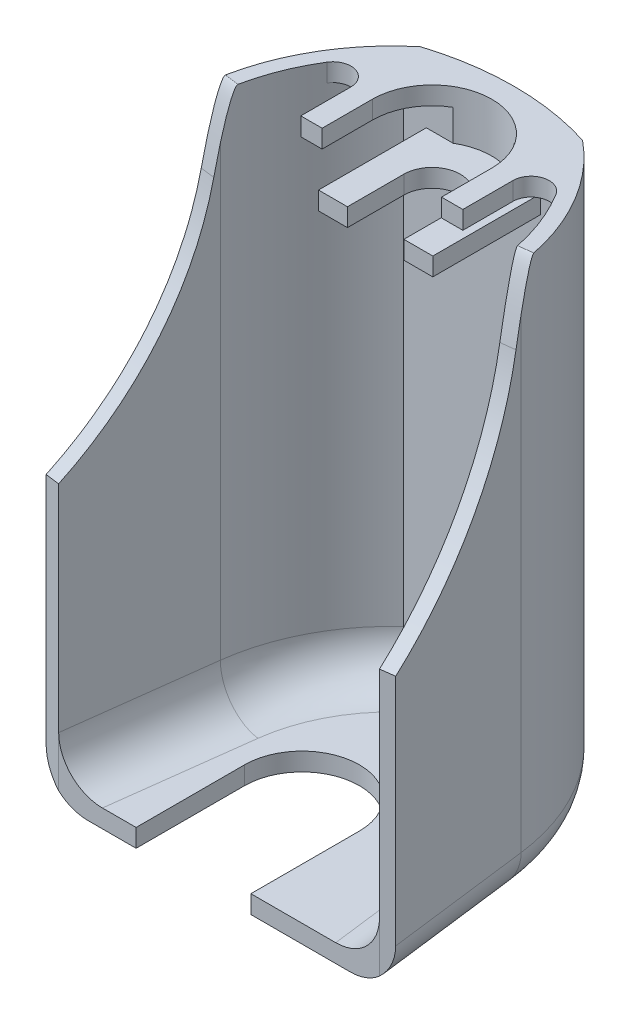
SolidWorks part; units mm, degrees
material "ABS"
ref_plane "Front Plane" through (0, 0, 0) normal (0, 0, 1) x (1, 0, 0)
ref_plane "Top Plane" through (0, 0, 0) normal (0, 1, 0) x (1, 0, 0)
ref_plane "Right Plane" through (0, 0, 0) normal (1, 0, 0) x (0, 0, -1)
sketch "Sketch1" plane through (0, 0, 0) normal (0, 1, 0) x (1, 0, 0)
  line L6 (-7.493, 9.017) -> (7.493, 9.017)
  line L10 (-4.953, 0) -> (-4.953, -7.493)
  line L11 (4.953, 0) -> (4.953, -7.493)
  line L14 (-7.493, -9.9072) -> (-4.953, -9.9072)
  line L15 (-4.953, -9.9072) -> (-4.953, -7.493)
  line L16 (4.953, -7.493) -> (4.953, -9.9072)
  line L17 (4.953, -9.9072) -> (7.493, -9.9072)
  line L19 (-7.493, 9.017) -> (-10.033, 9.017)
  line L20 (-10.033, 9.017) -> (-10.033, -9.9072)
  line L21 (-10.033, -9.9072) -> (-7.493, -9.9072)
  line L22 (7.493, 9.017) -> (10.033, 9.017)
  line L23 (10.033, 9.017) -> (10.033, -9.9072)
  line L24 (10.033, -9.9072) -> (7.493, -9.9072)
  arc A0 (4.953, 0) -> (-4.953, 0) centre (0, 0) ccw
  dimension "D1" = 4.953
  dimension "D9" = 2.54
  dimension "D5" = 18.9242
  dimension "D6" = 9.9072
  dimension "D8" = 9.9072
extrude "Boss-Extrude1" add sketch "Sketch1" along normal blind 3.175
sketch "Sketch2" plane through (0, 0, -9.017) normal (0, 0, -1) x (-1, 0, 0)
  line L12 (-10.033, 3.175) -> (10.033, 3.175) construction
  line L17 (-14.224, 11.811) -> (14.224, 11.811)
  line L19 (14.224, 11.811) -> (14.224, -85.4217)
  line L20 (14.224, -85.4217) -> (-14.224, -85.4217)
  line L21 (-14.224, -85.4217) -> (-14.224, 11.811)
  line L23 (7.493, 3.175) -> (7.493, 0) construction
  point P3 (0, 3.175)
  point P4 (0, 11.811)
  dimension "D1" = 6.731
  dimension "D2" = 8.636
  dimension "D3" = 8.636
  dimension "D4" = 14.224
  dimension "D5" = 14.224
extrude "Boss-Extrude2" add sketch "Sketch2" along normal blind 3.175
sketch "Sketch6" plane through (0, 0, -12.192) normal (0, 0, 1) x (1, 0, 0)
  line L6 (-14.224, 11.811) -> (14.224, 11.811) construction
  line L7 (14.224, 11.811) -> (14.224, -85.4217) construction
  line L22 (-14.224, 11.811) -> (14.224, 11.811)
  line L24 (14.224, 11.811) -> (14.224, 8.636)
  line L25 (-14.224, 8.636) -> (-14.224, 11.811)
  line L26 (-14.224, 8.636) -> (14.224, 8.636)
  line L28 (-14.224, -85.4217) -> (-14.224, 11.811) construction
  point P5 (3.4395, 11.811)
  dimension "D1" = 3.175
extrude "Boss-Extrude3" add sketch "Sketch6" along normal blind 21.0185
sketch "Sketch7" plane through (0, 11.811, 0) normal (0, 1, 0) x (1, 0, 0)
  line L0 (-10.4775, 0) -> (-10.4775, -8.8265)
  line L2 (14.224, -8.8265) -> (-14.224, -8.8265) construction
  line L3 (-10.4775, -8.8265) -> (10.4775, -8.8265)
  line L4 (10.4775, -8.8265) -> (10.4775, 0)
  arc A0 (10.4775, 0) -> (-10.4775, 0) centre (0, 0) ccw
extrude "Cut-Extrude1" cut sketch "Sketch7" against normal up to surface (8.636 mm away)
sketch "Sketch9" plane through (0, 11.811, 0) normal (0, 1, 0) x (1, 0, 0)
  line L1 (-14.224, -1003.1406) -> (-14.224, 48996.8594) construction
  line L5 (14.224, -1003.8381) -> (14.224, 48996.1619) construction
  line L7 (14.224, -8.8265) -> (14.224, 12.192) construction
  line L8 (-14.224, -8.8265) -> (-14.224, 12.192) construction
  line L9 (-10.4775, -8.8265) -> (-14.224, -8.8265) construction
  arc A0 (-14.224, 12.192) -> (14.224, 12.192) centre (0, -32.6257) cw
  arc A1 (-14.224, 12.192) -> (-27.4955, -11.8745) centre (9.4135, -16.5355) ccw
  arc A2 (14.224, 12.192) -> (27.4955, -11.8745) centre (-9.4135, -16.5355) cw
  dimension "D2" = 37.2022
  dimension "D3" = 37.2022
  dimension "D1" = 3.048
  dimension "D4" = 17.018
  dimension "D5" = 17.018
extrude "Extrude-Thin2" add sketch "Sketch9" against normal up to surface (97.2327 mm away) thin
fillet "Fillet3" radius 3.175 2 edges at (14.224, 10.2235, -8.8167) (-14.224, 10.2235, -8.8167)
sketch "Sketch14" plane through (0, -85.4217, 0) normal (0, -1, 0) x (1, 0, 0)
  line L0 (-24.9755, 12.1927) -> (24.9755, 12.1927)
  line L1 (-14.0073, -9.017) -> (14.0073, -9.017)
  arc A0 (24.9755, 12.1927) -> (14.0073, -9.017) centre (-9.4135, 16.5355) cw
  arc A1 (-24.9755, 12.1927) -> (-14.0073, -9.017) centre (9.4135, 16.5355) ccw
  dimension "D1" = 49.951
extrude "Boss-Extrude6" add sketch "Sketch14" against normal blind 3.175
sketch "Sketch16" plane through (-1.9076, 0, 15.1058) normal (-0.1253, 0, 0.9921) x (0.9921, 0, 0.1253)
  line L1 (-25.7911, 11.811) -> (-23.2511, 11.811)
  line L2 (-25.7911, 11.811) -> (-25.7911, -85.4217)
  line L3 (-25.7911, -85.4217) -> (-23.2511, -85.4217)
  line L4 (-23.2511, 11.811) -> (-23.2511, -85.4217)
extrude "Boss-Extrude7" add sketch "Sketch16" along normal blind 25.4
sketch "Sketch17" plane through (1.9076, 0, 15.1058) normal (0.1253, 0, 0.9921) x (0.9921, 0, -0.1253)
  line L1 (23.2511, 11.811) -> (25.7911, 11.811)
  line L2 (23.2511, 11.811) -> (23.2511, -85.4217)
  line L3 (23.2511, -85.4217) -> (25.7911, -85.4217)
  line L4 (25.7911, 11.811) -> (25.7911, -85.4217)
extrude "Boss-Extrude8" add sketch "Sketch17" along normal blind 25.4
sketch "Sketch18" plane through (25.5879, 0, -3.2313) normal (0.9921, 0, -0.1253) x (-0.1253, 0, -0.9921)
  line L0 (-40.6258, -85.4217) -> (-40.6258, 11.811) construction
  line L5 (-15.2258, -85.4217) -> (-15.2258, 11.811)
  line L6 (-15.2258, 11.811) -> (-40.6258, 11.811)
  line L7 (-40.6258, 11.811) -> (-40.6258, -85.4217)
  line L8 (-40.6258, -85.4217) -> (-15.2258, -85.4217)
  line L10 (-15.2258, 11.811) -> (-40.6258, 11.811)
  line L11 (-40.6258, 11.811) -> (-40.6258, -36.8054)
  arc A0 (-15.2258, 11.811) -> (-40.6258, -36.8054) centre (-71.078, 10.048) cw
  dimension "D1" = 55.88
  dimension "D2" = 0
extrude "Cut-Extrude2" cut sketch "Sketch18" against normal up to surface (2.54 mm away)
sketch "Sketch20" plane through (-25.5879, 0, -3.2313) normal (-0.9921, 0, -0.1253) x (-0.1253, 0, 0.9921)
  line L0 (40.6258, 11.811) -> (40.6258, -85.4217) construction
  arc A0 (15.2258, 11.811) -> (40.6258, -36.8054) centre (71.078, 10.048) ccw
  dimension "D1" = 55.88
extrude "Cut-Extrude3" cut sketch "Sketch20" against normal blind 10.922 and the other way through all
fillet "Fillet4" radius 13.335 2 edges
sketch "Sketch24" plane through (0, -85.4217, 0) normal (0, -1, 0) x (1, 0, 0)
  line L0 (-28.1578, 37.3926) -> (28.1578, 37.3926)
  line L1 (28.1578, 37.3926) -> (24.9755, 12.1927)
  line L2 (24.9755, 12.1927) -> (-24.9755, 12.1927)
  line L3 (-24.9755, 12.1927) -> (-28.1578, 37.3926)
extrude "Boss-Extrude10" add sketch "Sketch24" against normal blind 3.175
sketch "Sketch26" plane through (0, -85.4217, 0) normal (0, -1, 0) x (1, 0, 0)
  line L0 (-14.5674, 37.3926) -> (-14.5674, 18.3426)
  line L1 (28.1578, 37.3926) -> (-28.1578, 37.3926) construction
  line L2 (5.5814, 18.3426) -> (5.5814, 37.3926)
  line L3 (5.5814, 37.3926) -> (-14.5674, 37.3926)
  arc A0 (-14.5674, 18.3426) -> (-11.0955, 10.7334) centre (-4.493, 18.3426) ccw
  arc A1 (-11.0955, 10.7334) -> (5.5814, 18.3426) centre (-4.493, 18.3426) ccw
  dimension "D1" = 19.05
  dimension "D2" = 13.5904
extrude "Cut-Extrude6" cut sketch "Sketch26" against normal up to surface (3.175 mm away) up to face at (-0.8652, -82.2467, 17.2279)
fillet "Fillet9" radius 7.62 5 edges at (-29.0867, -85.4217, 24.4744) (-23.1636, -85.4217, -1.4292) (0, -85.4217, -14.395) (23.1636, -85.4217, -1.4292) (29.0867, -85.4217, 24.4744)
fillet "Fillet10" radius 7.62 5 edges at (21.3754, -82.2467, 0.6136) (0, -82.2467, -9.017) (26.5667, -82.2467, 24.7927)
equation "\"D3@Sketch9\"=\"D2@Sketch9\""
equation "\"D5@Sketch9\"=\"D4@Sketch9\""
